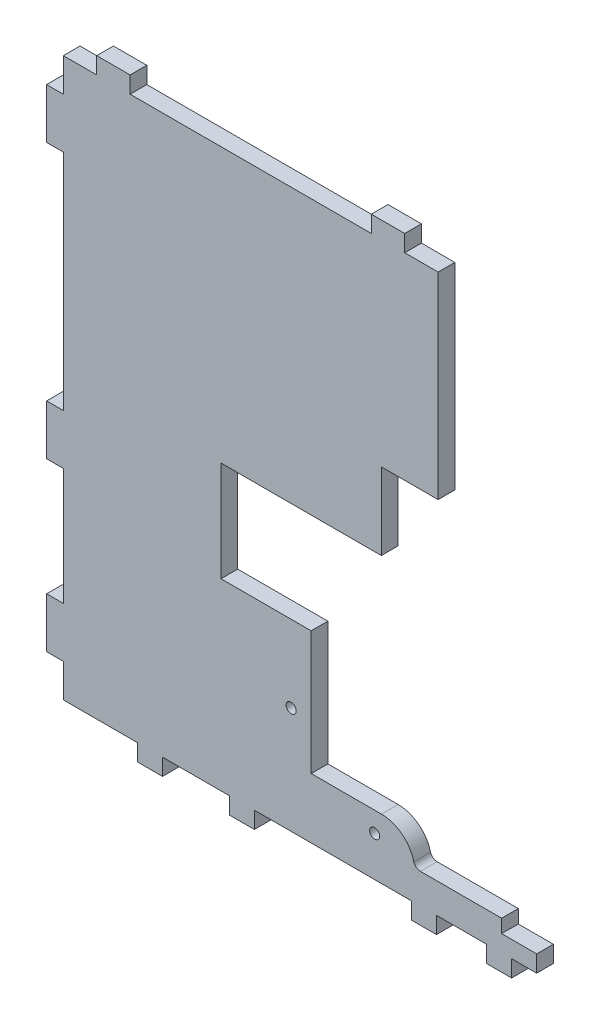
SolidWorks part; units mm, degrees
ref_plane "Plan de face" through (0, 0, 0) normal (0, 0, 1) x (1, 0, 0)
ref_plane "Plan de dessus" through (0, 0, 0) normal (0, 1, 0) x (1, 0, 0)
ref_plane "Plan de droite" through (0, 0, 0) normal (1, 0, 0) x (0, 0, -1)
sketch "Esquisse1" plane through (0, 0, 0) normal (0, 0, 1) x (1, 0, 0)
  line L1 (0, 0) -> (37, 0)
  line L2 (0, 0) -> (0, 55)
  line L3 (0, 55) -> (12, 55)
  line L4 (37, 0) -> (37, 18)
  line L6 (12, 55) -> (12, 18)
  line L7 (12, 18) -> (37, 18)
  circle A0 centre (6, 32) radius 1.5
  circle A1 centre (31, 12) radius 1.5
  dimension "D3" = 20
  dimension "D4" = 3
  dimension "D1" = 6
  dimension "D2" = 55
  dimension "D5" = 12
  dimension "D7" = 25
  dimension "D8" = 6
  dimension "D9" = 6
extrude "Boss.-Extru.1" add sketch "Esquisse1" along normal blind 5
sketch "Esquisse2" plane through (0, 0, 5) normal (0, 0, 1) x (1, 0, 0)
  line L0 (37, 18) -> (12, 18) construction
  line L1 (37, 0) -> (42, 0)
  line L2 (37, 0) -> (37, 18)
  line L3 (49.5, 0) -> (64.5, 0)
  line L4 (12, 55) -> (0, 55) construction
  line L5 (72, 0) -> (72, -5)
  line L6 (72, -5) -> (64.5, -5)
  line L7 (64.5, 0) -> (64.5, -5)
  line L8 (72, 0) -> (79.5, 0)
  line L9 (49.5, 0) -> (49.5, -5)
  line L10 (49.5, -5) -> (42, -5)
  line L11 (42, 0) -> (42, -5)
  line L12 (0, 0) -> (-5, 0)
  line L13 (0, 0) -> (0, 55)
  line L14 (0, 55) -> (-15, 55)
  line L15 (40, 167) -> (50, 167)
  line L16 (-12.5, 0) -> (-32.5, 0)
  line L17 (-40, 0) -> (-40, -5)
  line L18 (-15, 55) -> (-15, 85)
  line L19 (-40, -5) -> (-32.5, -5)
  line L20 (-62.19, 0) -> (-62.19, 10)
  line L21 (-62.19, 167) -> (-52.19, 167)
  line L22 (-32.5, 0) -> (-32.5, -5)
  line L23 (33, 85) -> (-15, 85)
  line L24 (50, 167) -> (50, 108)
  line L25 (-12.5, 0) -> (-12.5, -5)
  line L26 (-12.5, -5) -> (-5, -5)
  line L27 (-5, 0) -> (-5, -5)
  line L28 (-40, 0) -> (-62.19, 0)
  line L29 (-52.19, 167) -> (-52.19, 172)
  line L30 (-52.19, 172) -> (-42.19, 172)
  line L31 (-42.19, 167) -> (-42.19, 172)
  line L32 (-42.19, 167) -> (30, 167)
  line L33 (40, 167) -> (40, 172)
  line L34 (40, 172) -> (30, 172)
  line L35 (30, 167) -> (30, 172)
  line L36 (-62.19, 157) -> (-62.19, 167)
  line L37 (-62.19, 10) -> (-67.19, 10)
  line L38 (33, 85) -> (33, 108)
  line L39 (33, 108) -> (50, 108)
  line L40 (37, 18) -> (43, 18)
  line L41 (-62.19, 25) -> (-67.19, 25)
  line L42 (-67.19, 10) -> (-67.19, 25)
  line L43 (-62.19, 60) -> (-67.19, 60)
  line L44 (-62.19, 25) -> (-62.19, 60)
  line L45 (-62.19, 75) -> (-67.19, 75)
  line L46 (-67.19, 60) -> (-67.19, 75)
  line L47 (-62.19, 157) -> (-67.19, 157)
  line L48 (-62.19, 75) -> (-62.19, 142)
  line L49 (-62.19, 142) -> (-67.19, 142)
  line L50 (-67.19, 157) -> (-67.19, 142)
  line L51 (79.5, 0) -> (79.5, 5)
  line L52 (43, 18) -> (43, 9)
  line L53 (43, 9) -> (69, 9)
  line L56 (69, 9) -> (69, 5)
  line L57 (69, 5) -> (79.5, 5)
  circle A0 centre (31, 12) radius 1.5 construction
  dimension "D24" = 3
  dimension "D25" = 12
  dimension "D1" = 42.5
  dimension "D2" = 7.5
  dimension "D3" = 5
  dimension "D4" = 5
  dimension "D5" = 15
  dimension "D6" = 15
  dimension "D7" = 30
  dimension "D8" = 167
  dimension "D9" = 23
  dimension "D10" = 5
  dimension "D11" = 20
  dimension "D12" = 62.19
  dimension "D13" = 50
  dimension "D14" = 5
  dimension "D15" = 10
  dimension "D16" = 10
  dimension "D17" = 10
  dimension "D18" = 17
  dimension "D19" = 10
  dimension "D20" = 10
  dimension "D21" = 35
  dimension "D22" = 15
  dimension "D23" = 5
  dimension "D26" = 5
  dimension "D27" = 26
extrude "Boss.-Extru.2" add sketch "Esquisse2" against normal blind 5
fillet "Congé1" radius 10 1 edges at (43, 18, 2.5)
fillet "Congé2" radius 2 1 edges at (43, 9, 2.5)
